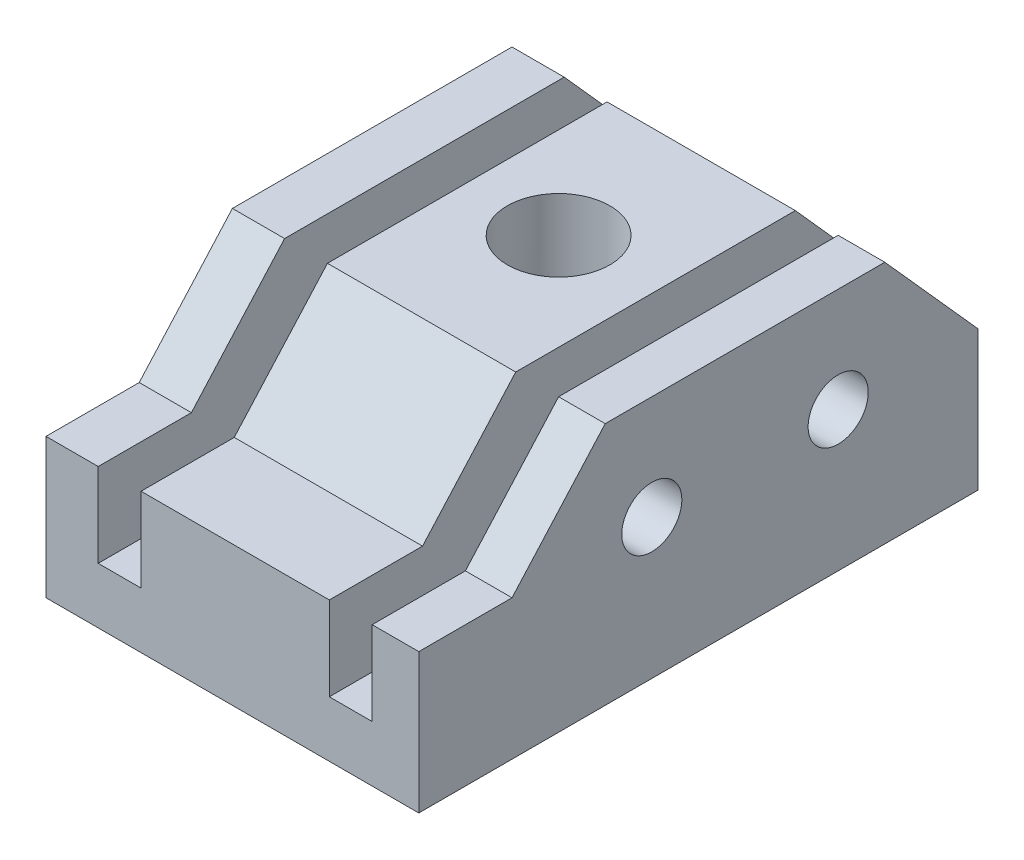
SolidWorks part; units mm, degrees
ref_plane "Front Plane" through (0, 0, 0) normal (0, 0, 1) x (1, 0, 0)
ref_plane "Top Plane" through (0, 0, 0) normal (0, 1, 0) x (1, 0, 0)
ref_plane "Right Plane" through (0, 0, 0) normal (1, 0, 0) x (0, 0, -1)
sketch "Sketch1" plane through (0, 0, 0) normal (1, 0, 0) x (0, 0, -1)
  line L1 (0, 0) -> (63.5, 0)
  line L2 (0, 0) -> (0, 6.35)
  line L3 (0, 6.35) -> (63.5, 6.35)
  line L4 (63.5, 0) -> (63.5, 6.35)
  dimension "D1" = 6.35
  dimension "D2" = 63.5
extrude "Boss-Extrude1" add sketch "Sketch1" against normal blind 50.8
sketch "Sketch2" plane through (0, 0, 0) normal (1, 0, 0) x (0, 0, -1)
  line L0 (0, 6.35) -> (0, 19.05)
  line L1 (0, 19.05) -> (12.7, 33.249)
  line L2 (12.7, 33.249) -> (50.8, 33.249)
  line L3 (50.8, 33.249) -> (63.5, 19.05)
  line L4 (63.5, 19.05) -> (63.5, 6.35)
  line L5 (63.5, 6.35) -> (0, 6.35)
  point P7 (31.75, 33.249)
  point P10 (31.75, 6.35)
  dimension "D1" = 38.1
  dimension "D2" = 12.7
  dimension "D3" = 12.7
  dimension "D4" = 19.05
  dimension "D5" = 19.05
extrude "Boss-Extrude2" add sketch "Sketch2" against normal blind 50.8
sketch "Sketch10" plane through (0, 0, -63.5) normal (0, 0, -1) x (-1, 0, 0)
  line L1 (50.8, 33.249) -> (0, 33.249) construction
  line L3 (6.35, 7.62) -> (6.35, 33.249)
  line L4 (6.35, 33.249) -> (12.192, 33.249)
  line L5 (12.192, 7.62) -> (12.192, 33.249)
  line L6 (6.35, 7.62) -> (12.192, 7.62)
  line L8 (50.8, 0) -> (0, 0) construction
  point P11 (12.192, 7.62)
  dimension "D1" = 7.62
  dimension "D2" = 5.842
  dimension "D3" = 6.35
extrude "Cut-Extrude1" cut sketch "Sketch10" against normal through all
pattern_linear "LPattern3" count 2 spacing 31.496 along (-1, 0, 0) of "Cut-Extrude1"
sketch "Sketch11" plane through (0, 0, 0) normal (1, 0, 0) x (0, 0, -1)
  circle A0 centre (19.05, 19.05) radius 4.0957
  circle A1 centre (19.05, 19.05) radius 7.9375 construction
  circle A2 centre (44.45, 19.05) radius 4.0958
  circle A3 centre (44.45, 19.05) radius 7.9375 construction
  dimension "D1" = 8.1915
  dimension "D3" = 15.875
  dimension "D4" = 8.1915
  dimension "D6" = 15.875
  dimension "D2" = 6.35
  dimension "D5" = 6.35
extrude "Cut-Extrude2" cut sketch "Sketch11" against normal through all
sketch "Sketch14" plane through (0, 33.249, 0) normal (0, 1, 0) x (1, 0, 0)
  line L3 (-37.846, 12.7) -> (-37.846, 50.8) construction
  point P0 (-25.4, 31.75)
  point P4 (-37.846, 31.75)
  dimension "D1" = 12.446
sketch "Sketch17" plane through (0, 40.0201, -44.7438) normal (0, 0.6667, -0.7454) x (-1, 0, 0)
  line L0 (12.192, -28.1343) -> (12.192, -9.0843) construction
  line L1 (37.846, -9.0843) -> (12.192, -9.0843) construction
  point P0 (25.019, -18.6093)
  point P4 (12.192, -18.6093)
  point P7 (25.019, -9.0843)
sketch "Sketch18" plane through (0, 8.4667, 9.466) normal (0, 0.6667, 0.7454) x (1, 0, 0)
  line L0 (-12.192, 33.249) -> (-12.192, 14.199) construction
  line L1 (-37.846, 33.249) -> (-12.192, 33.249) construction
  point P0 (-25.019, 23.724)
  point P1 (-25.019, 23.724)
  point P4 (-12.192, 23.724)
  point P7 (-25.019, 33.249)
ref_plane "Plane2" through (0, 33.02, 0) normal (0, -1, 0) x (-1, 0, 0)
fillet "Fillet1" [suppressed] radius 2.54
sketch "Sketch22" plane through (0, 0, 0) normal (0, 0, 1) x (1, 0, 0)
  line L0 (-50.8, 19.05) -> (-50.8, 0) construction
  line L1 (0, 0) -> (-50.8, 0)
  line L2 (0, 0) -> (0, 7.62)
  line L3 (-6.35, 7.62) -> (-12.192, 7.62)
  line L4 (-50.8, 0) -> (-50.8, 7.62)
  line L5 (-37.846, 7.62) -> (-37.846, 19.05)
  line L6 (-37.846, 19.05) -> (-12.192, 19.05)
  line L7 (-12.192, 19.05) -> (-12.192, 7.62)
  line L8 (-37.846, 7.62) -> (-43.688, 7.62)
  line L9 (-50.8, 7.62) -> (-50.8, 19.05)
  line L10 (-50.8, 19.05) -> (-43.688, 19.05)
  line L11 (-43.688, 19.05) -> (-43.688, 7.62)
  line L12 (-6.35, 7.62) -> (-6.35, 19.05)
  line L13 (-6.35, 19.05) -> (0, 19.05)
  line L14 (0, 19.05) -> (0, 7.62)
extrude "Boss-Extrude3" add sketch "Sketch22" along normal blind 12.7
sketch "Sketch23" plane through (0, 33.249, 0) normal (0, 1, 0) x (1, 0, 0)
  line L0 (-25.4, 63.5) -> (-25.4, -12.7) construction
  line L1 (-50.8, 63.5) -> (0, 63.5) construction
  line L2 (-50.8, -12.7) -> (0, -12.7) construction
  circle A0 centre (-25.4, 31.75) radius 6.985
  point P15 (-34.579, 50.8)
  dimension "D1" = 13.97
extrude "Cut-Extrude6" cut sketch "Sketch23" against normal through all
sketch "Sketch24" plane through (0, 0, 0) normal (0, -1, 0) x (1, 0, 0)
  line L0 (-25.4, -63.5) -> (-25.4, 12.7) construction
  line L1 (-13.97, -50.8) -> (-36.83, -50.8)
  line L2 (-13.97, -50.8) -> (-13.97, 7.62)
  line L3 (-13.97, 7.62) -> (-36.83, 7.62)
  line L4 (-36.83, -50.8) -> (-36.83, 7.62)
  line L5 (-50.8, -63.5) -> (0, -63.5) construction
  line L6 (-50.8, 12.7) -> (0, 12.7) construction
  line L7 (-25.4, -50.8) -> (-25.4, 7.62) construction
  circle A0 centre (-25.4, -31.75) radius 6.985 construction
  dimension "D1" = 58.42
  dimension "D2" = 19.05
  dimension "D3" = 22.86
extrude "Cut-Extrude7" cut sketch "Sketch24" against normal blind 4.58
sketch "Sketch25" plane through (0, 4.58, 0) normal (0, -1, 0) x (1, 0, 0)
  circle A0 centre (-25.4, -31.75) radius 7
  dimension "D1" = 14
extrude "Cut-Extrude8" cut sketch "Sketch25" against normal blind 2.8
sketch "Sketch26" plane through (0, 4.58, 0) normal (0, -1, 0) x (-1, 0, 0)
  line L0 (25.4, 50.8) -> (25.4, -7.62) construction
  line L1 (36.83, 50.8) -> (13.97, 50.8) construction
  line L2 (13.97, -7.62) -> (36.83, -7.62) construction
  circle A0 centre (30.4, 46.15) radius 3
  circle A1 centre (20.4, 46.15) radius 3
  circle A2 centre (25.4, 31.75) radius 7 construction
  circle A3 centre (20.4, -1.897) radius 3
  circle A4 centre (30.4, -1.897) radius 3
  dimension "D2" = 6
  dimension "D5" = 5
  dimension "D1" = 14.4
  dimension "D3" = 10
  dimension "D4" = 10
extrude "Cut-Extrude9" cut sketch "Sketch26" against normal blind 10
